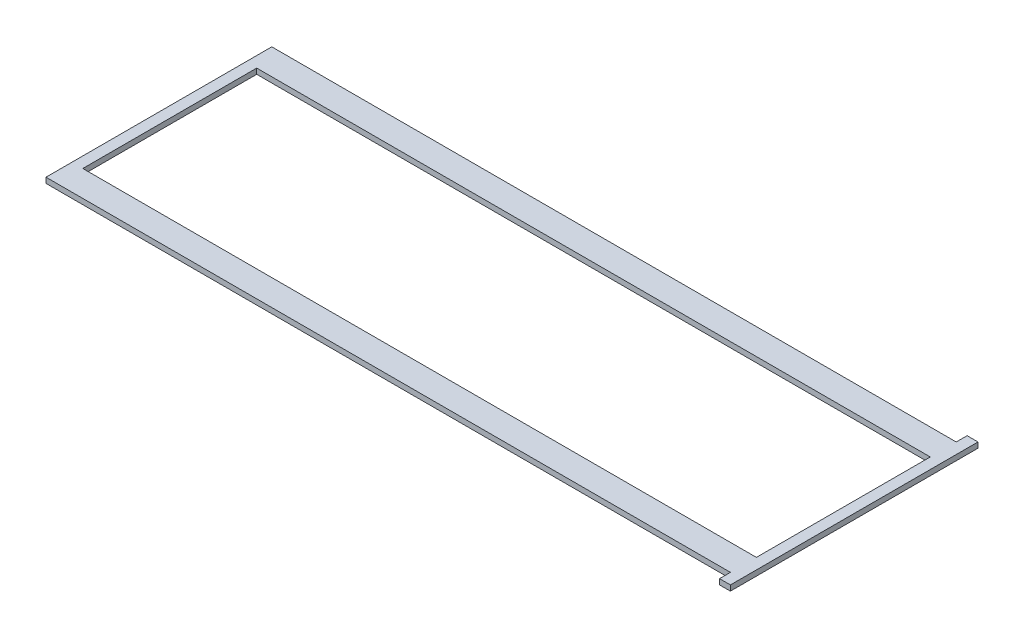
SolidWorks part; units mm, degrees
ref_plane "Front" through (0, 0, 0) normal (0, 0, 1) x (1, 0, 0)
ref_plane "Top" through (0, 0, 0) normal (0, 1, 0) x (1, 0, 0)
ref_plane "Right" through (0, 0, 0) normal (1, 0, 0) x (0, 0, -1)
sketch "Sketch1" plane through (0, 0, 0) normal (0, 1, 0) x (1, 0, 0)
  line L1 (-203.2, -72.3614) -> (203.2, -72.3614)
  line L2 (-203.2, -72.3614) -> (-203.2, 72.3614)
  line L3 (-203.2, 72.3614) -> (203.2, 72.3614)
  line L4 (203.2, -72.3614) -> (203.2, 72.3614)
  line L5 (-203.2, -72.3614) -> (203.2, 72.3614) construction
  line L6 (-203.2, 72.3614) -> (203.2, -72.3614) construction
  line L7 (-203.2, 72.3614) -> (196.85, 72.3614)
  line L8 (-203.2, 72.3614) -> (-203.2, 65.986)
  line L9 (-203.2, 65.986) -> (196.85, 65.986)
  line L10 (196.85, 72.3614) -> (196.85, 65.986)
  line L11 (-203.2, -72.3614) -> (196.85, -72.3614)
  line L12 (-203.2, -72.3614) -> (-203.2, -65.986)
  line L13 (-203.2, -65.986) -> (196.85, -65.986)
  line L14 (196.85, -72.3614) -> (196.85, -65.986)
  line L15 (-196.85, -50.8254) -> (196.85, -50.8254)
  line L16 (-196.85, -50.8254) -> (-196.85, 50.8254)
  line L17 (-196.85, 50.8254) -> (196.85, 50.8254)
  line L18 (196.85, -50.8254) -> (196.85, 50.8254)
  line L19 (-196.85, -50.8254) -> (196.85, 50.8254) construction
  line L20 (-196.85, 50.8254) -> (196.85, -50.8254) construction
  point P0 (0, 0)
  point P12 (0, 0)
  dimension "D1" = 144.7228
  dimension "D2" = 406.4
  dimension "D3" = 6.35
  dimension "D4" = 6.3754
  dimension "D5" = 101.6508
extrude "Boss-Extrude1" add sketch "Sketch1" along normal blind 3.175 contours L14 L1 L4 L3 L10 L9 L2 L13 L18 L15 L16 L17 region at (201.164, 0, 69.1737)
equation "\"D1@Sketch1\"= 4.98025 - 0.002 + 2 * ( 0.25 + 0.016 + ( 6 / 64 ) )"
